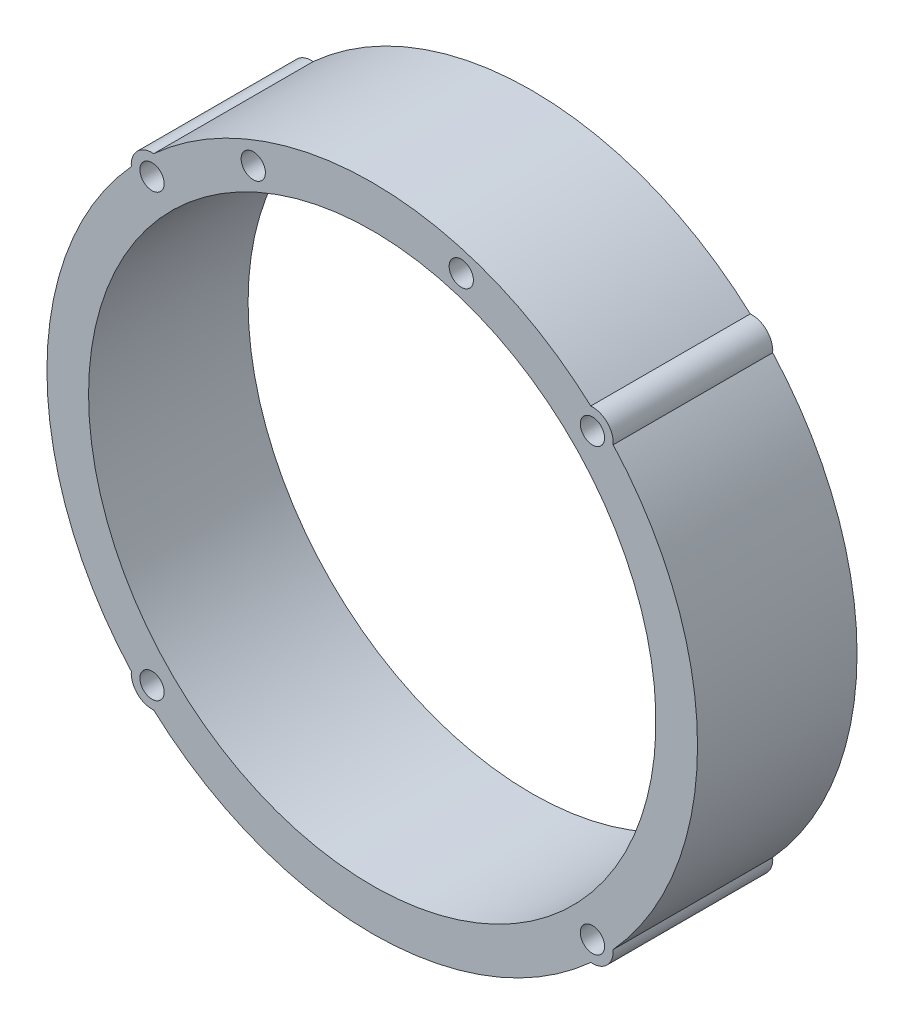
SolidWorks part; units mm, degrees
material "ABS"
ref_plane "前视基准面" through (0, 0, 0) normal (0, 0, 1) x (1, 0, 0)
ref_plane "上视基准面" through (0, 0, 0) normal (0, 1, 0) x (1, 0, 0)
ref_plane "右视基准面" through (0, 0, 0) normal (1, 0, 0) x (0, 0, -1)
sketch "草图1" plane through (0, 0, 0) normal (0, 0, 1) x (1, 0, 0)
  line L0 (-9.35, 50.0979) -> (9.35, 50.0979) construction
  line L1 (0, 50.0979) -> (0, 0) construction
  line L2 (-9.35, 50.0979) -> (-10.85, 50.0979) construction
  line L3 (9.35, 50.0979) -> (11.35, 50.0979) construction
  line L4 (0, 0) -> (12.8351, 41.9818) construction
  arc A0 (-17.6706, 36.8858) -> (7.8297, 40.1436) centre (0, 0) ccw
  arc A1 (-17.6706, 36.8858) -> (-9.35, 50.0979) centre (-24, 50.0979) ccw construction
  arc A2 (7.8297, 40.1436) -> (9.35, 50.0979) centre (-24, 50.0979) ccw construction
  arc A3 (-30.6806, 27.0465) -> (0, 50.0979) centre (-24, 50.0979) ccw construction
  arc A7 (11.1055, 45.9474) -> (11.35, 50.0979) centre (-24, 50.0979) ccw construction
  circle A8 centre (0, 0) radius 34 construction
  arc A15 (11.8433, 44.8631) -> (15.0201, 43.9017) centre (0, 0) cw construction
  arc A17 (15.6798, 42.774) -> (15.1953, 40.514) centre (-24, 50.0979) cw construction
  circle A18 centre (0, 0) radius 43.9 construction
  circle A19 centre (12.8351, 41.9818) radius 1.75
  circle A20 centre (36.8176, 23.9097) radius 1.75 construction
  circle A21 centre (43.5728, -5.3501) radius 1.75 construction
  circle A22 centre (29.9397, -32.1064) radius 1.75 construction
  circle A23 centre (2.2975, -43.8398) radius 1.75 construction
  circle A24 centre (-26.4197, -35.0601) radius 1.75 construction
  circle A25 centre (-42.7748, -9.8754) radius 1.75 construction
  circle A26 centre (-39.1152, 19.9302) radius 1.75 construction
  circle A27 centre (-17.1531, 40.4102) radius 1.75
  arc A29 (-13.3104, 42.4393) -> (-10.85, 50.0979) centre (-24, 50.0979) ccw construction
  arc A30 (-14.8807, 42.3688) -> (-13.3104, 42.4393) centre (-14.1233, 43.0217) ccw construction
  arc A32 (15.7942, 39.3485) -> (15.1953, 40.514) centre (16.1667, 40.2765) cw construction
  arc A33 (15.0201, 43.9017) -> (15.6798, 42.774) centre (14.6964, 42.9555) cw construction
  arc A34 (11.8433, 44.8631) -> (11.1055, 45.9474) centre (12.0986, 45.83) cw construction
  arc A35 (-17.6706, 36.8858) -> (7.8297, 40.1436) centre (0, 0) cw
  circle A43 centre (0, 0) radius 46.9
  point P39 (0, 0)
  dimension "D1" = 81.8
  dimension "D3" = 24
  dimension "D4" = 6
  dimension "D5" = 2
  dimension "D6" = 68
  dimension "D7" = 3
  dimension "D8" = 5.5
  dimension "D9" = 5
  dimension "D10" = 9
  dimension "D11" = 17
  dimension "D13" = 3.5
  dimension "D15" = 1
  dimension "D16" = 1
  dimension "D2" = 9.35
  dimension "D14" = 9.35
extrude "凸台-拉伸1" add sketch "草图1" along normal blind 23
sketch "草图2" plane through (0, 0, 23) normal (0, 0, 1) x (1, 0, 0)
  circle A0 centre (0, 0) radius 44.9 construction
  circle A1 centre (-31.7491, 31.7491) radius 3
  circle A2 centre (31.7491, 31.7491) radius 3
  circle A3 centre (31.7491, -31.7491) radius 3
  circle A4 centre (-31.7491, -31.7491) radius 3
  point P15 (0, 0)
  dimension "D2" = 6
  dimension "D3" = 89.8
  dimension "D1" = 4
extrude "凸台-拉伸2" add sketch "草图2" against normal up to surface (23 mm away) up to face at (46.9, 0, 0)
sketch "草图3" plane through (0, 0, 23) normal (0, 0, 1) x (1, 0, 0)
  circle A0 centre (-31.7491, 31.7491) radius 1.75
  circle A1 centre (-31.7491, -31.7491) radius 1.75
  circle A2 centre (31.7491, -31.7491) radius 1.75
  circle A3 centre (31.7491, 31.7491) radius 1.75
  dimension "D1" = 3.5
extrude "切除-拉伸1" cut sketch "草图3" against normal through all
